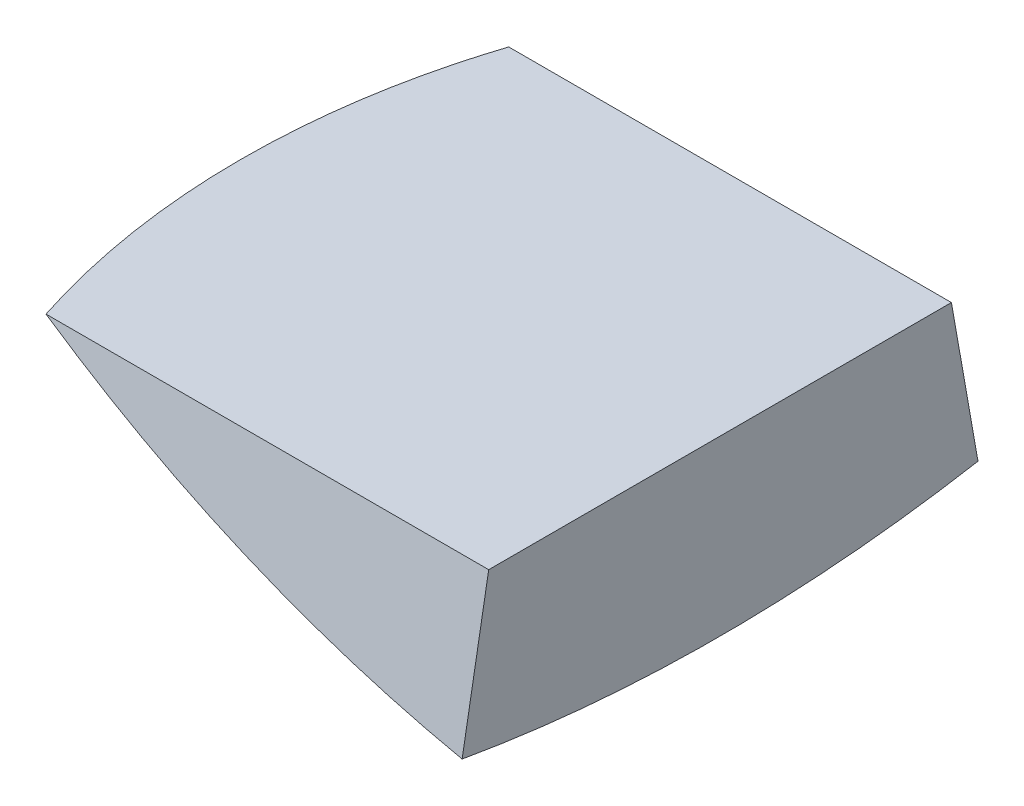
SolidWorks part; units mm, degrees
material "Polyurethane Foam Rigid"
ref_plane "Front Plane" through (0, 0, 0) normal (0, 0, 1) x (1, 0, 0)
ref_plane "Top Plane" through (0, 0, 0) normal (0, 1, 0) x (1, 0, 0)
ref_plane "Right Plane" through (0, 0, 0) normal (1, 0, 0) x (0, 0, -1)
sketch "Sketch1" plane through (0, 0, 0) normal (0, 0, 1) x (1, 0, 0)
  line L0 (-132.3199, -750.4235) -> (-132.3199, -648.8235)
  line L1 (0, 0) -> (0, -17.1989) construction
  line L2 (0, 0) -> (0, -324.9103) construction
  line L3 (0, 0) -> (-132.3199, -750.4235) construction
  line L4 (-132.3199, -648.8235) -> (-399.5899, -648.8235)
  line L5 (0, 0) -> (-376.3803, 0) construction
  line L6 (0, 11.5765) -> (-387.6987, 11.5765) construction
  arc A0 (-132.3199, -750.4235) -> (-399.5899, -648.8235) centre (0, 0) cw
  dimension "D2" = 762
  dimension "D1" = 10
  dimension "D3" = 101.6
  dimension "D4" = 762
revolve "Revolve1" add sketch "Sketch1" angle 20 mid plane about L6
sketch "Sketch2" plane through (-132.3199, 0, 0) normal (1, 0, 0) x (0, 0, -1)
  line L1 (-217.2973, -505.5801) -> (197.3972, -505.5801)
  line L2 (-217.2973, -505.5801) -> (-217.2973, -661.5235)
  line L3 (-217.2973, -661.5235) -> (197.3972, -661.5235)
  line L4 (197.3972, -505.5801) -> (197.3972, -661.5235)
  arc A1 (-132.3199, -738.847) -> (132.3199, -738.847) centre (0, 11.5765) ccw construction
  point P4 (0, -750.4235)
  dimension "D1" = 88.9
extrude "Cut-Extrude1" cut sketch "Sketch2" against normal through all
equation "\"gapAngle\"= 10deg"
equation "\"D1@Sketch1\"=\"gapAngle\""
equation "\"LegFront\"= 30in"
equation "\"D2@Sketch1\"=\"LegFront\""
equation "\"LegSide\"= 30in"
equation "\"D4@Sketch1\"=\"LegSide\""
